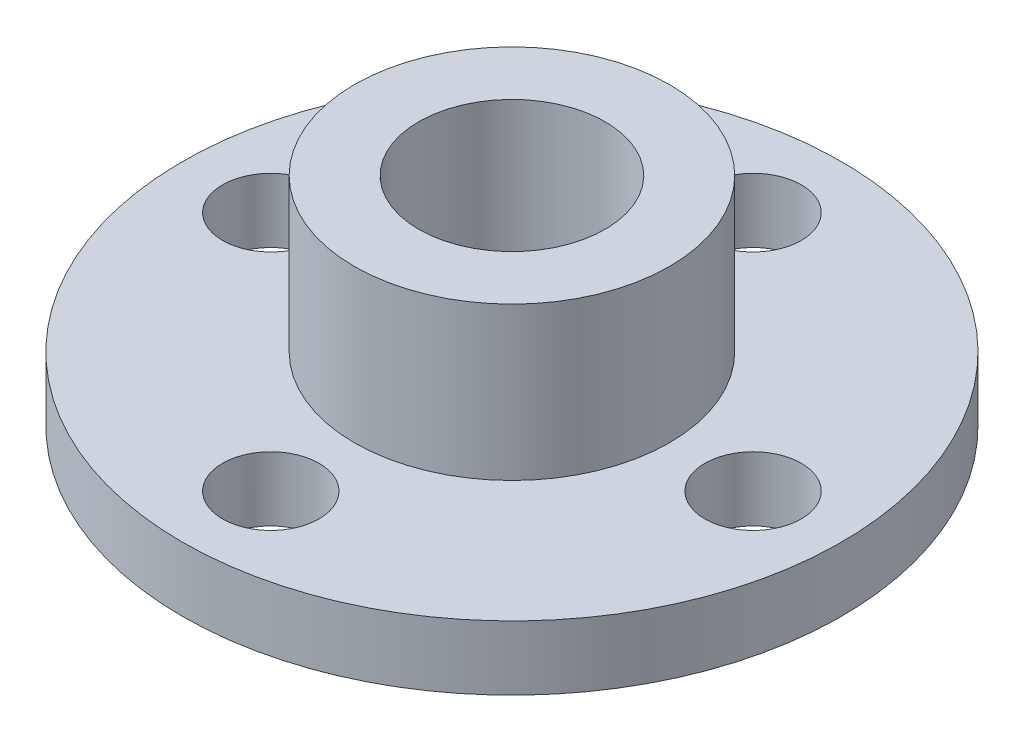
SolidWorks part; units mm, degrees
ref_plane "Front Plane" through (0, 0, 0) normal (0, 0, 1) x (1, 0, 0)
ref_plane "Top Plane" through (0, 0, 0) normal (0, 1, 0) x (1, 0, 0)
ref_plane "Right Plane" through (0, 0, 0) normal (1, 0, 0) x (0, 0, -1)
sketch "Sketch1" plane through (0, 0, 0) normal (0, 1, 0) x (1, 0, 0)
  circle A0 centre (0, 0) radius 10.25
  dimension "D1" = 20.5
extrude "Boss-Extrude1" add sketch "Sketch1" along normal blind 2
sketch "Sketch2" plane through (0, 2, 0) normal (0, 1, 0) x (1, 0, 0)
  line L0 (0, 0) -> (10.25, 0) construction
  line L1 (0, 0) -> (0, 10.25) construction
  line L2 (0, 0) -> (7.2478, 7.2478) construction
  line L3 (0, 0) -> (7.2478, -7.2478) construction
  circle A0 centre (0, 0) radius 10.25 construction
  circle A1 centre (7.5, 0) radius 1.5
  circle A2 centre (0, 0) radius 1.5
  circle A3 centre (0, 7.5) radius 1.5
  circle A4 centre (-7.5, 0) radius 1.5
  circle A5 centre (0, -7.5) radius 1.5
  dimension "D1" = 3
  dimension "D2" = 7.5
extrude "Cut-Extrude1" cut sketch "Sketch2" against normal blind 3
sketch "Sketch3" plane through (0, 2, 0) normal (0, 1, 0) x (1, 0, 0)
  circle A0 centre (0, 0) radius 2.9
  circle A1 centre (0, 0) radius 4.9
  dimension "D1" = 5.8
  dimension "D2" = 2
extrude "Boss-Extrude2" add sketch "Sketch3" along normal blind 4.75 contours A1 | A0
